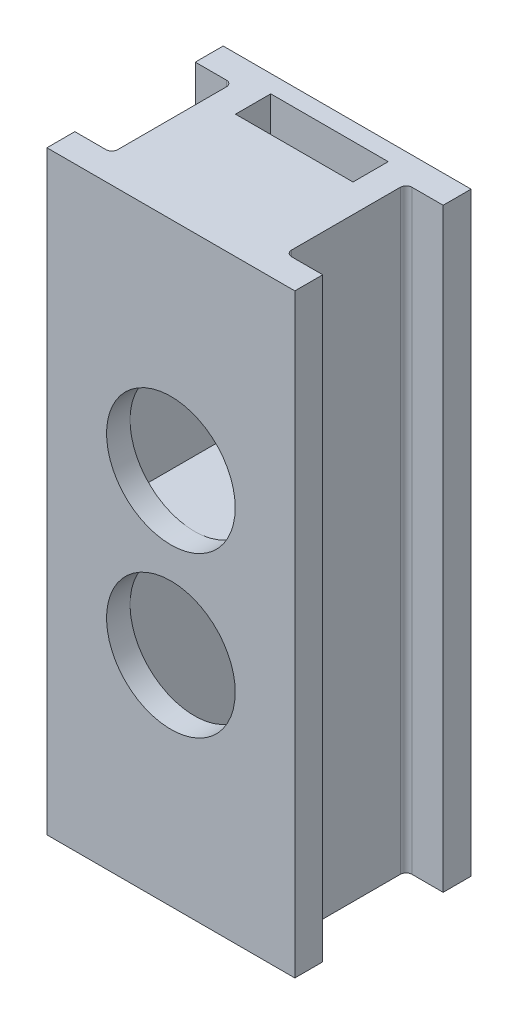
SolidWorks part; units mm, degrees
ref_plane "Front Plane" through (0, 0, 0) normal (0, 0, 1) x (1, 0, 0)
ref_plane "Top Plane" through (0, 0, 0) normal (0, 1, 0) x (1, 0, 0)
ref_plane "Right Plane" through (0, 0, 0) normal (1, 0, 0) x (0, 0, -1)
sketch "Sketch1" plane through (0, 0, 0) normal (0, 0, 1) x (1, 0, 0)
  line L0 (5.55, 29.125) -> (-5.55, 29.125)
  line L1 (5.55, 8.125) -> (5.55, 29.125)
  line L2 (-5.55, 8.125) -> (5.55, 8.125)
  line L3 (-5.55, 29.125) -> (-5.55, 8.125)
  line L4 (10.55, -18.525) -> (-10.55, -18.525)
  line L5 (10.55, -18.525) -> (10.55, 32.125)
  line L6 (10.55, 32.125) -> (-10.55, 32.125)
  line L7 (5.55, 5.475) -> (-5.55, 5.475)
  line L8 (5.55, -15.525) -> (5.55, 5.475)
  line L9 (-5.55, -15.525) -> (5.55, -15.525)
  line L10 (-5.55, 5.475) -> (-5.55, -15.525)
  line L11 (-10.55, -18.525) -> (-10.55, 32.125)
  line L12 (-7.55, 15.35) -> (-7.55, -36.6)
  line L13 (7.55, 15.35) -> (7.55, -36.6)
  line L14 (-7.4, 15.35) -> (-7.4, -36.6)
  line L15 (7.4, 15.35) -> (7.4, -36.6)
  circle A0 centre (0, 0) radius 5.475
  circle A1 centre (0, 13.6) radius 5.475
sketch "Sketch2" plane through (0, 0, 0) normal (0, 0, 1) x (1, 0, 0)
  line L0 (-10.55, -18.525) -> (-10.55, 32.125) construction
  line L1 (10.55, 32.125) -> (-10.55, 32.125) construction
  line L2 (10.55, -18.525) -> (10.55, 32.125) construction
  line L3 (10.55, -18.525) -> (-10.55, -18.525) construction
  line L4 (-10.55, -18.525) -> (-10.55, 32.125)
  line L5 (10.55, 32.125) -> (-10.55, 32.125)
  line L6 (10.55, -18.525) -> (10.55, 32.125)
  line L7 (10.55, -18.525) -> (-10.55, -18.525)
  circle A0 centre (0, 0) radius 5.475 construction
  circle A1 centre (0, 13.6) radius 5.475 construction
  circle A2 centre (0, 0) radius 5.475
  circle A3 centre (0, 13.6) radius 5.475
  point P10 (-7.4, 15.35)
  point P11 (7.4, 15.35)
extrude "Boss-Extrude1" add sketch "Sketch2" along normal mid plane 15
sketch "Sketch3" plane through (0, 32.125, 0) normal (0, 1, 0) x (1, 0, 0)
  line L0 (-10.55, -7.5) -> (-10.55, 7.5) construction
  line L1 (-10.55, 5.125) -> (-7.4, 5.125)
  line L2 (-10.55, 5.125) -> (-10.55, -5.125)
  line L3 (-10.55, -5.125) -> (-7.4, -5.125)
  line L4 (-7.4, 5.125) -> (-7.4, -5.125)
  point P6 (-10.55, 0)
  dimension "D1" = 10.25
extrude "Cut-Extrude1" cut sketch "Sketch3" against normal through all both and the other way through all
mirror "Mirror1" about plane through (0, 0, 0) normal (1, 0, 0) of "Cut-Extrude1"
sketch "Sketch4" plane through (0, 0, -7.5) normal (0, 0, -1) x (-1, 0, 0)
  line L0 (-5.55, -15.525) -> (-5.55, 5.475) construction
  line L1 (-5.55, 5.475) -> (5.55, 5.475) construction
  line L2 (5.55, 5.475) -> (5.55, -15.525) construction
  line L3 (5.55, -15.525) -> (-5.55, -15.525) construction
  line L4 (-5.55, 8.125) -> (-5.55, 29.125) construction
  line L5 (-5.55, 29.125) -> (5.55, 29.125) construction
  line L6 (5.55, 29.125) -> (5.55, 8.125) construction
  line L7 (5.55, 8.125) -> (-5.55, 8.125) construction
  line L8 (-5.55, -15.525) -> (-5.55, 5.475)
  line L9 (-5.55, 5.475) -> (5.55, 5.475)
  line L10 (5.55, 5.475) -> (5.55, -15.525)
  line L11 (5.55, -15.525) -> (-5.55, -15.525)
  line L12 (-5.55, 8.125) -> (-5.55, 29.125)
  line L13 (-5.55, 29.125) -> (5.55, 29.125)
  line L14 (5.55, 29.125) -> (5.55, 8.125)
  line L15 (5.55, 8.125) -> (-5.55, 8.125)
extrude "Cut-Extrude2" cut sketch "Sketch4" against normal blind 13
sketch "Sketch5" plane through (0, 0, -7.5) normal (0, 0, -1) x (-1, 0, 0)
  line L0 (0, 8.125) -> (0, 5.475) construction
  line L1 (-5.55, 8.125) -> (5.55, 8.125) construction
  line L2 (5.55, 5.475) -> (-5.55, 5.475) construction
  circle A0 centre (0, 6.8) radius 0.5 construction
  point P10 (0, 6.8)
  dimension "D1" = 1
fillet "Fillet1" radius 0.5 4 edges at (-7.4, 6.8, -5.125) (-7.4, 6.8, 5.125) (7.4, 6.8, -5.125) (7.4, 6.8, 5.125)
sketch "Sketch6" plane through (0, 32.125, 0) normal (0, 1, 0) x (1, 0, 0)
  line L1 (-5, 6) -> (5, 6)
  line L2 (-5, 6) -> (-5, 3)
  line L3 (-5, 3) -> (5, 3)
  line L4 (5, 6) -> (5, 3)
  point P4 (0, 6)
  dimension "D1" = 3
  dimension "D2" = 3
  dimension "D3" = 10
extrude "Cut-Extrude3" cut sketch "Sketch6" against normal up to surface (24 mm away) and the other way through all up to face at (0, 8.125, 0.3)
extrude "Cut-Extrude4" cut sketch "Sketch6<2>" along normal up to surface (-26.65 mm away) from surface up to face at (0, 5.475, 0.3) starting at face at (0, -18.525, 0)
sketch "Sketch6<2>" plane through (0, 32.125, 0) normal (0, 1, 0) x (1, 0, 0) same geometry as "Sketch6"
sketch "Sketch7" plane through (0, 0, 5.5) normal (0, 0, -1) x (-1, 0, 0)
  line L0 (5.55, 8.125) -> (5.55, 29.125) construction
  line L1 (-5.55, 29.125) -> (5.55, 29.125)
  line L2 (-5.55, 29.125) -> (-5.55, 24.125)
  line L3 (-5.55, 24.125) -> (5.55, 24.125)
  line L4 (5.55, 29.125) -> (5.55, 24.125)
  line L5 (5.55, -15.525) -> (5.55, 5.475) construction
  line L6 (-5.55, -15.525) -> (5.55, -15.525)
  line L7 (-5.55, -15.525) -> (-5.55, -10.525)
  line L8 (-5.55, -10.525) -> (5.55, -10.525)
  line L9 (5.55, -15.525) -> (5.55, -10.525)
  dimension "D1" = 5
extrude "Cut-Extrude5" cut sketch "Sketch7" against normal blind 1
